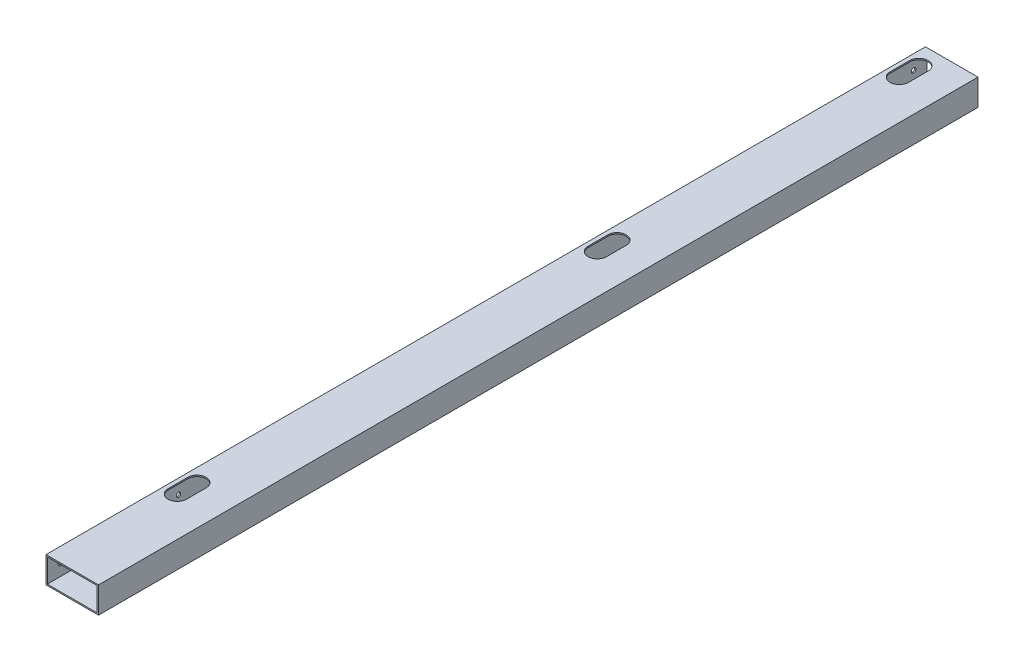
SolidWorks part; units mm, degrees
material "1060 合金"
ref_plane "前视基准面" through (0, 0, 0) normal (0, 0, 1) x (1, 0, 0)
ref_plane "上视基准面" through (0, 0, 0) normal (0, 1, 0) x (1, 0, 0)
ref_plane "右视基准面" through (0, 0, 0) normal (1, 0, 0) x (0, 0, -1)
other "Configuration Table"
sketch "草图1" plane through (0, 0, 0) normal (0, 0, 1) x (1, 0, 0)
  line L1 (0, 0) -> (40, 0)
  line L2 (0, 0) -> (0, -20)
  line L3 (0, -20) -> (40, -20)
  line L4 (40, 0) -> (40, -20)
  dimension "D1" = 20
  dimension "D2" = 40
extrude "拉伸-薄壁1" add sketch "草图1" along normal blind 670 thin thin type one direction reverse wall 1
sketch "草图4" plane through (0, 0, 0) normal (-1, 0, 0) x (0, 0, 1)
  line L0 (670, 0) -> (0, 0) construction
  line L1 (670, 0) -> (670, -20) construction
  line L4 (0, -180.2783) -> (0, 689.7217) construction
  circle A1 centre (659.9964, -10) radius 1.75
  circle A49 centre (10, -10) radius 1.75
  dimension "D27" = 3.5
  dimension "D28" = 3.5
  dimension "D29" = 10
  dimension "D25" = 10
  dimension "D26" = 10.0036
  dimension "D30" = 10
extrude "切除-拉伸2" cut sketch "草图4" against normal blind 1.5
sketch "草图5" plane through (0, 0, 0) normal (-1, 0, 0) x (0, 0, 1)
  circle A0 centre (42.5, -10) radius 1.75 construction
  circle A1 centre (42.5, -10) radius 1.75
  circle A2 centre (62.5, -10) radius 1.75
  circle A3 centre (82.5, -10) radius 1.75
  circle A4 centre (102.5, -10) radius 1.75
  circle A5 centre (122.5, -10) radius 1.75
  circle A6 centre (142.5, -10) radius 1.75
  circle A7 centre (162.5, -10) radius 1.75
  circle A8 centre (182.5, -10) radius 1.75
  circle A9 centre (202.5, -10) radius 1.75
  circle A10 centre (222.5, -10) radius 1.75
  circle A11 centre (242.5, -10) radius 1.75
  circle A12 centre (262.5, -10) radius 1.75
  circle A13 centre (282.5, -10) radius 1.75
  circle A14 centre (302.5, -10) radius 1.75
  circle A15 centre (322.5, -10) radius 1.75
  circle A16 centre (342.5, -10) radius 1.75
  circle A17 centre (362.5, -10) radius 1.75
  circle A18 centre (382.5, -10) radius 1.75
  circle A19 centre (402.5, -10) radius 1.75
  circle A20 centre (422.5, -10) radius 1.75
  circle A21 centre (442.5, -10) radius 1.75
  circle A22 centre (462.5, -10) radius 1.75
  circle A23 centre (482.5, -10) radius 1.75
  dimension "D1" = 23
sketch "草图6" plane through (40, 0, 0) normal (1, 0, 0) x (0, 0, -1)
  line L0 (-670, -20) -> (0, -20) construction
  line L1 (-670, -20) -> (-670, 0) construction
  circle A0 centre (-440, -10) radius 2.5
  circle A1 centre (-230, -10) radius 2.5
  dimension "D1" = 5
  dimension "D2" = 5
  dimension "D3" = 10
  dimension "D4" = 10
  dimension "D5" = 230
  dimension "D6" = 230
sketch "草图7" plane through (0, 0, 0) normal (-1, 0, 0) x (0, 0, 1)
  line L0 (670, -20) -> (0, -20) construction
  line L1 (0, 0) -> (0, -20) construction
  circle A0 centre (190, -10) radius 1.6
  circle A1 centre (170, -10) radius 1.6
  dimension "D1" = 3.2
  dimension "D2" = 3.2
  dimension "D3" = 10
  dimension "D4" = 10
  dimension "D5" = 170
  dimension "D6" = 20
sketch "草图8" plane through (0, 0, 0) normal (-1, 0, 0) x (0, 0, 1)
  line L0 (670, 0) -> (0, 0) construction
  line L1 (0, 0) -> (0, -20) construction
  circle A0 centre (55, -10) radius 1.65
  circle A1 centre (265, -10) radius 1.65
  dimension "D2" = 3.3
  dimension "D1" = 10
  dimension "D3" = 55
  dimension "D4" = 2
extrude "切除-拉伸3" cut sketch "草图8" against normal blind 5
sketch "草图9" plane through (0, 0, 0) normal (-1, 0, 0) x (0, 0, 1)
  line L0 (670, 0) -> (670, -20) construction
  line L1 (670, 0) -> (0, 0) construction
  circle A0 centre (570, -10) radius 1.6
  dimension "D2" = 3.2
  dimension "D1" = 100
  dimension "D3" = 10
extrude "切除-拉伸4" cut sketch "草图9" against normal blind 10
sketch "草图10" plane through (0, 0, 0) normal (0, 1, 0) x (1, 0, 0)
  line L0 (10, -580) -> (10, -565) construction
  line L1 (3, -580) -> (3, -565)
  line L2 (17, -580) -> (17, -565)
  line L3 (0, -670) -> (0, 0) construction
  line L4 (40, -670) -> (0, -670) construction
  line L5 (10, -30) -> (10, -15) construction
  line L6 (3, -30) -> (3, -15)
  line L7 (17, -30) -> (17, -15)
  arc A0 (3, -580) -> (17, -580) centre (10, -580) ccw
  arc A1 (17, -565) -> (3, -565) centre (10, -565) ccw
  arc A2 (3, -30) -> (17, -30) centre (10, -30) ccw
  arc A3 (17, -15) -> (3, -15) centre (10, -15) ccw
  point P2 (10, -572.5)
  point P15 (10, -22.5)
  dimension "D2" = 7
  dimension "D1" = 10
  dimension "D3" = 15
  dimension "D4" = 90
  dimension "D5" = 2
extrude "切除-拉伸5" cut sketch "草图10" against normal blind 10
pattern_linear "阵列(线性)1" count 2 spacing 230 along (0, 0, 1) of "切除-拉伸5"
